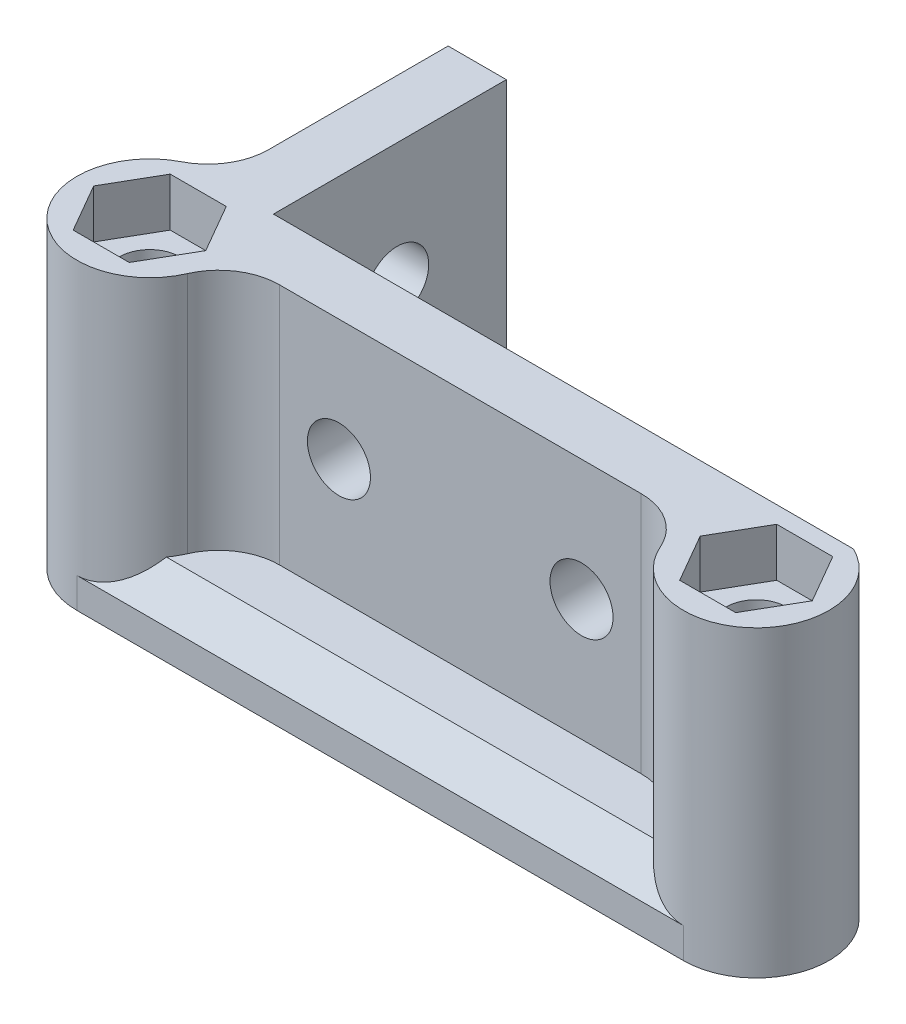
SolidWorks part; units mm, degrees
ref_plane "Front Plane" through (0, 0, 0) normal (0, 0, 1) x (1, 0, 0)
ref_plane "Top Plane" through (0, 0, 0) normal (0, 1, 0) x (1, 0, 0)
ref_plane "Right Plane" through (0, 0, 0) normal (1, 0, 0) x (0, 0, -1)
sketch "Sketch1" plane through (0, 0, 0) normal (0, 1, 0) x (1, 0, 0)
  line L0 (0, -6) -> (50, -6)
  line L1 (47.3847, 5.4) -> (25.7, 5.4)
  line L2 (0, 9.798) -> (0, 24.6)
  line L3 (0, 24.6) -> (6.5, 24.6)
  line L4 (6.5, 24.6) -> (25.7, 5.4)
  arc A0 (-2.7273, 5.3443) -> (0, -6) centre (0, 0) ccw
  arc A1 (50, -6) -> (47.3847, 5.4) centre (50, 0) ccw
  arc A2 (-2.7273, 5.3443) -> (0, 9.798) centre (-5, 9.798) ccw
  dimension "D1" = 12
  dimension "D2" = 12
  dimension "D3" = 50
  dimension "D5" = 10
  dimension "D4" = 11.4
  dimension "D6" = 30.6
  dimension "D7" = 6.5
  dimension "D8" = 45
extrude "Boss-Extrude1" add sketch "Sketch1" along normal blind 4.8
sketch "Sketch2" plane through (0, 4.8, 0) normal (0, 1, 0) x (1, 0, 0)
  line L0 (0, 24.6) -> (4.8, 24.6)
  line L1 (6.5, 24.6) -> (0, 24.6) construction
  line L2 (4.8, 24.6) -> (4.8, 5.4)
  line L3 (4.8, 5.4) -> (52.6153, 5.4)
  line L5 (47.3847, 5.4) -> (25.7, 5.4) construction
  line L6 (0, 24.6) -> (0, 9.798) construction
  line L7 (0, 24.6) -> (0, 9.798)
  line L8 (10.0817, 0.6) -> (39.9183, 0.6)
  arc A0 (50, -6) -> (47.3847, 5.4) centre (50, 0) ccw construction
  arc A1 (-2.7273, 5.3443) -> (0, 9.798) centre (-5, 9.798) ccw construction
  arc A2 (-2.7273, 5.3443) -> (0, 9.798) centre (-5, 9.798) ccw
  arc A3 (-2.7273, 5.3443) -> (5.4991, -2.4) centre (0, 0) ccw
  arc A4 (10.0817, 0.6) -> (5.4991, -2.4) centre (10.0817, -4.4) ccw
  arc A5 (44.5009, -2.4) -> (39.9183, 0.6) centre (39.9183, -4.4) ccw
  arc A6 (44.5009, -2.4) -> (52.6153, 5.4) centre (50, 0) ccw
  point P2 (10.3938, 0.5902)
  point P19 (39.0545, 0.5248)
  point P21 (-10.0817, -4.4)
  point P29 (9.6846, -5.2162)
  dimension "D2" = 4.8
  dimension "D3" = 10
  dimension "D5" = 10
  dimension "D1" = 4.8
extrude "Boss-Extrude2" add sketch "Sketch2" along normal blind 20.2
sketch "Sketch3" plane through (0, 4.8, 0) normal (0, 1, 0) x (1, 0, 0)
  line L2 (39.9183, 0.6) -> (10.0817, 0.6)
  line L3 (0, -6) -> (50, -6)
  line L4 (39.9183, 0.6) -> (10.0817, 0.6)
  line L5 (0, -6) -> (50, -6)
  arc A4 (44.5009, -2.4) -> (50, -6) centre (50, 0) ccw
  arc A5 (44.5009, -2.4) -> (39.9183, 0.6) centre (39.9183, -4.4) ccw
  arc A6 (10.0817, 0.6) -> (5.4991, -2.4) centre (10.0817, -4.4) ccw
  arc A7 (0, -6) -> (5.4991, -2.4) centre (0, 0) ccw
  arc A8 (44.5009, -2.4) -> (50, -6) centre (50, 0) ccw
  arc A9 (44.5009, -2.4) -> (39.9183, 0.6) centre (39.9183, -4.4) ccw
  arc A10 (10.0817, 0.6) -> (5.4991, -2.4) centre (10.0817, -4.4) ccw
  arc A11 (0, -6) -> (5.4991, -2.4) centre (0, 0) ccw
  dimension "D1" = 0
extrude "Boss-Extrude3" add sketch "Sketch3" along normal blind 0.2
chamfer "Chamfer1" distance 2.5 angle 45 1 edges at (25, 5, 6)
sketch "Sketch4" plane through (0, 0, 0) normal (0, -1, 0) x (1, 0, 0)
  circle A0 centre (0, 0) radius 2.5
  circle A1 centre (50, 0) radius 2.5
  arc A2 (47.3847, -5.4) -> (50, 6) centre (50, 0) ccw construction
  dimension "D1" = 5
  dimension "D2" = 5
extrude "Cut-Extrude1" cut sketch "Sketch4" against normal through all
sketch "Sketch5" plane through (0, 25, 0) normal (0, 1, 0) x (1, 0, 0)
  line L1 (4.6188, 0) -> (2.3094, 4)
  line L2 (2.3094, 4) -> (-2.3094, 4)
  line L3 (-2.3094, 4) -> (-4.6188, 0)
  line L4 (-4.6188, 0) -> (-2.3094, -4)
  line L5 (-2.3094, -4) -> (2.3094, -4)
  line L6 (2.3094, -4) -> (4.6188, 0)
  line L8 (9.655, 0) -> (41.2278, 0) construction
  line L9 (39.9183, 0.6) -> (10.0817, 0.6) construction
  line L11 (47.6906, 4) -> (45.3812, 0)
  line L12 (45.3812, 0) -> (47.6906, -4)
  line L13 (47.6906, -4) -> (52.3094, -4)
  line L14 (52.3094, -4) -> (54.6188, 0)
  line L15 (54.6188, 0) -> (52.3094, 4)
  line L16 (52.3094, 4) -> (47.6906, 4)
  circle A0 centre (0, 0) radius 4 construction
  circle A1 centre (50, 0) radius 4 construction
  arc A2 (44.5009, -2.4) -> (52.6153, 5.4) centre (50, 0) ccw construction
  point P25 (0, 0)
  dimension "D1" = 8
  dimension "D2" = 0.6
  dimension "D3" = 8
extrude "Cut-Extrude2" cut sketch "Sketch5" against normal blind 4
sketch "Sketch6" plane through (0, 0, -5.4) normal (0, 0, -1) x (-1, 0, 0)
  line L0 (-52.6153, 25) -> (-4.8, 25) construction
  line L1 (-4.8, 25) -> (-4.8, 4.8) construction
  circle A0 centre (-35, 15) radius 2.6
  circle A1 centre (-15, 15) radius 2.6
  dimension "D1" = 5.2
  dimension "D2" = 5.2
  dimension "D3" = 10
  dimension "D4" = 10
  dimension "D5" = 20
  dimension "D6" = 10.2
extrude "Cut-Extrude3" cut sketch "Sketch6" against normal through all
sketch "Sketch7" plane through (4.8, 0, 0) normal (1, 0, 0) x (0, 0, -1)
  line L0 (5.4, 25) -> (24.6, 25) construction
  line L1 (24.6, 25) -> (24.6, 4.8) construction
  circle A0 centre (15.6, 15) radius 2.6
  dimension "D1" = 5.2
  dimension "D2" = 10
  dimension "D3" = 9
extrude "Cut-Extrude4" cut sketch "Sketch7" against normal through all
